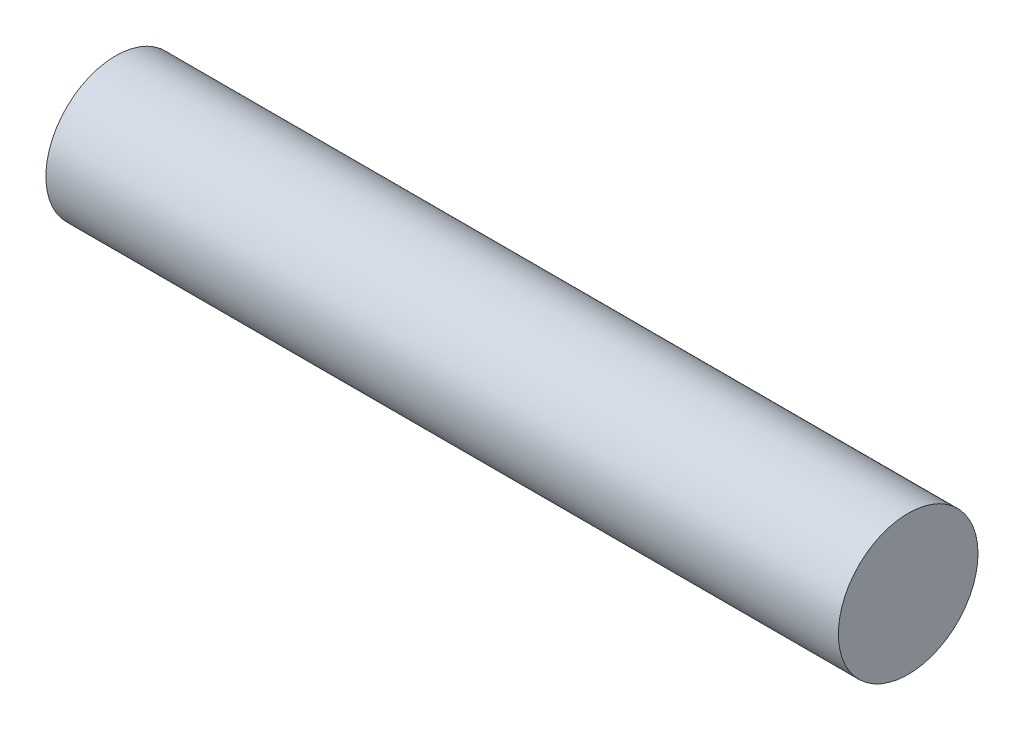
SolidWorks part; units mm, degrees
ref_plane "Front Plane" through (0, 0, 0) normal (0, 0, 1) x (1, 0, 0)
ref_plane "Top Plane" through (0, 0, 0) normal (0, 1, 0) x (1, 0, 0)
ref_plane "Right Plane" through (0, 0, 0) normal (1, 0, 0) x (0, 0, -1)
sketch "Sketch1" plane through (0, 0, 0) normal (1, 0, 0) x (0, 0, -1)
  circle A0 centre (0, 0) radius 13.9352
  dimension "D1" = 27.8704
extrude "Boss-Extrude1" add sketch "Sketch1" against normal blind 158.149
